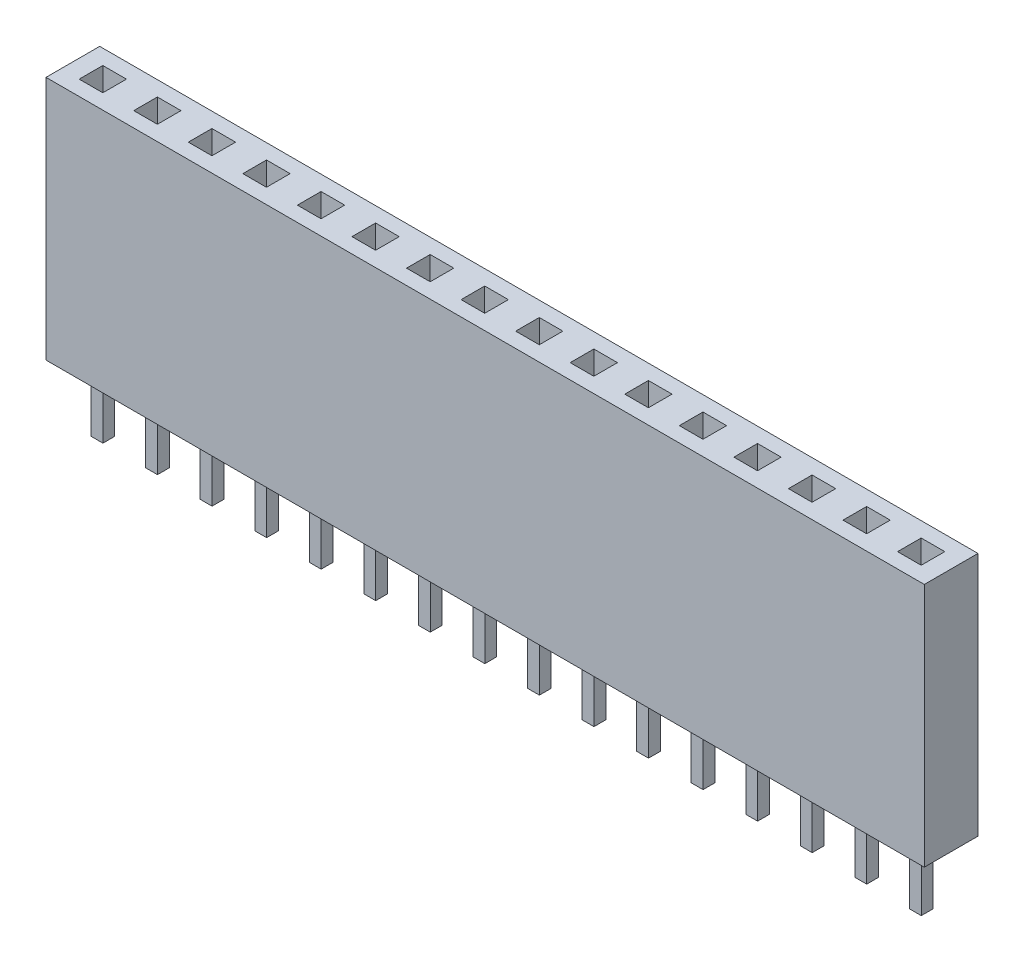
SolidWorks part; units mm, degrees
ref_plane "Front Plane" through (0, 0, 0) normal (0, 0, 1) x (1, 0, 0)
ref_plane "Top Plane" through (0, 0, 0) normal (0, 1, 0) x (1, 0, 0)
ref_plane "Right Plane" through (0, 0, 0) normal (1, 0, 0) x (0, 0, -1)
sketch "Sketch1" plane through (0, 0, 0) normal (0, 0, 1) x (1, 0, 0)
  line L1 (0, 0) -> (40.89, 0)
  line L2 (0, 0) -> (0, 11.4)
  line L3 (0, 11.4) -> (40.89, 11.4)
  line L4 (40.89, 0) -> (40.89, 11.4)
  dimension "D1" = 11.4
  dimension "D2" = 40.89
extrude "Boss-Extrude1" add sketch "Sketch1" along normal mid plane 2.5
sketch "Sketch2" plane through (0, 0, 0) normal (0, -1, 0) x (1, 0, 0)
  line L0 (0, 0) -> (40.89, 0) construction
  line L1 (40.89, 1.25) -> (40.89, -1.25) construction
  line L2 (3.385, -0.55) -> (4.485, -0.55)
  line L3 (0.845, -0.55) -> (1.945, -0.55)
  line L4 (0.845, -0.55) -> (0.845, 0.55)
  line L5 (0.845, 0.55) -> (1.945, 0.55)
  line L6 (1.945, -0.55) -> (1.945, 0.55)
  line L7 (0.845, -0.55) -> (1.945, 0.55) construction
  line L8 (0.845, 0.55) -> (1.945, -0.55) construction
  line L9 (3.385, -0.55) -> (3.385, 0.55)
  line L10 (3.385, 0.55) -> (4.485, 0.55)
  line L11 (4.485, -0.55) -> (4.485, 0.55)
  line L12 (3.385, -0.55) -> (4.485, 0.55) construction
  line L13 (3.385, 0.55) -> (4.485, -0.55) construction
  line L14 (5.925, -0.55) -> (7.025, -0.55)
  line L15 (5.925, -0.55) -> (5.925, 0.55)
  line L16 (5.925, 0.55) -> (7.025, 0.55)
  line L17 (7.025, -0.55) -> (7.025, 0.55)
  line L18 (5.925, -0.55) -> (7.025, 0.55) construction
  line L19 (5.925, 0.55) -> (7.025, -0.55) construction
  line L20 (8.465, -0.55) -> (9.565, -0.55)
  line L21 (8.465, -0.55) -> (8.465, 0.55)
  line L22 (8.465, 0.55) -> (9.565, 0.55)
  line L23 (9.565, -0.55) -> (9.565, 0.55)
  line L24 (8.465, -0.55) -> (9.565, 0.55) construction
  line L25 (8.465, 0.55) -> (9.565, -0.55) construction
  line L26 (11.005, -0.55) -> (12.105, -0.55)
  line L27 (11.005, -0.55) -> (11.005, 0.55)
  line L28 (11.005, 0.55) -> (12.105, 0.55)
  line L29 (12.105, -0.55) -> (12.105, 0.55)
  line L30 (11.005, -0.55) -> (12.105, 0.55) construction
  line L31 (11.005, 0.55) -> (12.105, -0.55) construction
  line L32 (13.545, -0.55) -> (14.645, -0.55)
  line L33 (13.545, -0.55) -> (13.545, 0.55)
  line L34 (13.545, 0.55) -> (14.645, 0.55)
  line L35 (14.645, -0.55) -> (14.645, 0.55)
  line L36 (13.545, -0.55) -> (14.645, 0.55) construction
  line L37 (13.545, 0.55) -> (14.645, -0.55) construction
  line L38 (16.085, -0.55) -> (17.185, -0.55)
  line L39 (16.085, -0.55) -> (16.085, 0.55)
  line L40 (16.085, 0.55) -> (17.185, 0.55)
  line L41 (17.185, -0.55) -> (17.185, 0.55)
  line L42 (16.085, -0.55) -> (17.185, 0.55) construction
  line L43 (16.085, 0.55) -> (17.185, -0.55) construction
  line L44 (18.625, -0.55) -> (19.725, -0.55)
  line L45 (18.625, -0.55) -> (18.625, 0.55)
  line L46 (18.625, 0.55) -> (19.725, 0.55)
  line L47 (19.725, -0.55) -> (19.725, 0.55)
  line L48 (18.625, -0.55) -> (19.725, 0.55) construction
  line L49 (18.625, 0.55) -> (19.725, -0.55) construction
  line L50 (21.165, -0.55) -> (22.265, -0.55)
  line L51 (21.165, -0.55) -> (21.165, 0.55)
  line L52 (21.165, 0.55) -> (22.265, 0.55)
  line L53 (22.265, -0.55) -> (22.265, 0.55)
  line L54 (21.165, -0.55) -> (22.265, 0.55) construction
  line L55 (21.165, 0.55) -> (22.265, -0.55) construction
  line L56 (23.705, -0.55) -> (24.805, -0.55)
  line L57 (23.705, -0.55) -> (23.705, 0.55)
  line L58 (23.705, 0.55) -> (24.805, 0.55)
  line L59 (24.805, -0.55) -> (24.805, 0.55)
  line L60 (23.705, -0.55) -> (24.805, 0.55) construction
  line L61 (23.705, 0.55) -> (24.805, -0.55) construction
  line L62 (26.245, -0.55) -> (27.345, -0.55)
  line L63 (26.245, -0.55) -> (26.245, 0.55)
  line L64 (26.245, 0.55) -> (27.345, 0.55)
  line L65 (27.345, -0.55) -> (27.345, 0.55)
  line L66 (26.245, -0.55) -> (27.345, 0.55) construction
  line L67 (26.245, 0.55) -> (27.345, -0.55) construction
  line L68 (28.785, -0.55) -> (29.885, -0.55)
  line L69 (28.785, -0.55) -> (28.785, 0.55)
  line L70 (28.785, 0.55) -> (29.885, 0.55)
  line L71 (29.885, -0.55) -> (29.885, 0.55)
  line L72 (28.785, -0.55) -> (29.885, 0.55) construction
  line L73 (28.785, 0.55) -> (29.885, -0.55) construction
  line L78 (1.395, 0) -> (3.935, 0) construction
  line L98 (31.325, -0.55) -> (32.425, -0.55)
  line L99 (31.325, -0.55) -> (31.325, 0.55)
  line L100 (31.325, 0.55) -> (32.425, 0.55)
  line L101 (32.425, -0.55) -> (32.425, 0.55)
  line L102 (33.865, -0.55) -> (34.965, -0.55)
  line L103 (33.865, -0.55) -> (33.865, 0.55)
  line L104 (33.865, 0.55) -> (34.965, 0.55)
  line L105 (34.965, -0.55) -> (34.965, 0.55)
  line L106 (36.405, -0.55) -> (37.505, -0.55)
  line L107 (36.405, -0.55) -> (36.405, 0.55)
  line L108 (36.405, 0.55) -> (37.505, 0.55)
  line L109 (37.505, -0.55) -> (37.505, 0.55)
  line L110 (38.945, -0.55) -> (40.045, -0.55)
  line L111 (38.945, -0.55) -> (38.945, 0.55)
  line L112 (38.945, 0.55) -> (40.045, 0.55)
  line L113 (40.045, -0.55) -> (40.045, 0.55)
  line L114 (31.325, -0.55) -> (32.425, 0.55) construction
  line L115 (31.325, 0.55) -> (32.425, -0.55) construction
  line L116 (33.865, -0.55) -> (34.965, 0.55) construction
  line L117 (33.865, 0.55) -> (34.965, -0.55) construction
  line L118 (36.405, -0.55) -> (37.505, 0.55) construction
  line L119 (36.405, 0.55) -> (37.505, -0.55) construction
  line L120 (38.945, -0.55) -> (40.045, 0.55) construction
  line L121 (38.945, 0.55) -> (40.045, -0.55) construction
  point P5 (1.395, 0)
  point P10 (36.955, 0)
  point P11 (34.415, 0)
  point P12 (3.935, 0)
  point P17 (6.475, 0)
  point P22 (9.015, 0)
  point P27 (11.555, 0)
  point P32 (14.095, 0)
  point P37 (16.635, 0)
  point P42 (19.175, 0)
  point P47 (21.715, 0)
  point P52 (24.255, 0)
  point P57 (26.795, 0)
  point P62 (29.335, 0)
  point P67 (39.495, 0)
  point P68 (31.875, 0)
  dimension "D1" = 1.1
  dimension "D3" = 1.395
  dimension "D4" = 2.54
  dimension "D2" = 16
extrude "Cut-Extrude1" cut sketch "Sketch2" against normal through all contours L3 L6 L5 L4 | L2 L11 L10 L9 | L14 L17 L16 L15 | L20 L23 L22 L21 | L26 L29 L28 L27 | L32 L35 L34 L33 | L38 L41 L40 L39 | L110 L113 L112 L111 | L106 L109 L108 L107 | L102 L105 L104 L103 | L98 L101 L100 L99 | L68 L71 L70 L69 | L62 L65 L64 L63 | L56 L59 L58 L57 | L50 L53 L52 L51 | L44 L47 L46 L45 region at (3.935, 0, 0) region at (1.395, 0, 0) region at (6.475, 0, 0) region at (9.015, 0, 0) region at (11.555, 0, 0) region at (14.095, 0, 0) region at (16.635, 0, 0) region at (19.175, 0, 0) region at (21.715, 0, 0) region at (24.255, 0, 0) region at (26.795, 0, 0) region at (29.335, 0, 0) region at (31.875, 0, 0) region at (34.415, 0, 0) region at (36.955, 0, 0) region at (39.495, 0, 0)
sketch "Sketch3" plane through (0, 0, 0) normal (0, -1, 0) x (1, 0, 0)
  line L1 (0, 1.25) -> (40.89, 1.25)
  line L2 (0, 1.25) -> (0, -1.25)
  line L3 (0, -1.25) -> (40.89, -1.25)
  line L4 (40.89, 1.25) -> (40.89, -1.25)
extrude "Boss-Extrude2" add sketch "Sketch3" against normal blind 1
sketch "Sketch4" plane through (0, 0, 0) normal (0, -1, 0) x (1, 0, 0)
  line L0 (1.125, 0) -> (1.675, 0) construction
  line L1 (1.125, 0.275) -> (1.675, 0.275)
  line L2 (1.125, 0.275) -> (1.125, -0.275)
  line L3 (1.125, -0.275) -> (1.675, -0.275)
  line L4 (1.675, 0.275) -> (1.675, -0.275)
  line L5 (0, 0) -> (40.89, 0) construction
  line L6 (40.89, 1.25) -> (40.89, -1.25) construction
  line L7 (0, 1.25) -> (0, -1.25) construction
  line L8 (3.665, 0.275) -> (3.665, -0.275)
  line L9 (3.665, 0.275) -> (4.215, 0.275)
  line L10 (3.665, -0.275) -> (4.215, -0.275)
  line L11 (4.215, 0.275) -> (4.215, -0.275)
  line L12 (6.205, 0.275) -> (6.205, -0.275)
  line L13 (6.205, 0.275) -> (6.755, 0.275)
  line L14 (6.205, -0.275) -> (6.755, -0.275)
  line L15 (6.755, 0.275) -> (6.755, -0.275)
  line L16 (8.745, 0.275) -> (8.745, -0.275)
  line L17 (8.745, 0.275) -> (9.295, 0.275)
  line L18 (8.745, -0.275) -> (9.295, -0.275)
  line L19 (9.295, 0.275) -> (9.295, -0.275)
  line L20 (11.285, 0.275) -> (11.285, -0.275)
  line L21 (11.285, 0.275) -> (11.835, 0.275)
  line L22 (11.285, -0.275) -> (11.835, -0.275)
  line L23 (11.835, 0.275) -> (11.835, -0.275)
  line L24 (13.825, 0.275) -> (13.825, -0.275)
  line L25 (13.825, 0.275) -> (14.375, 0.275)
  line L26 (13.825, -0.275) -> (14.375, -0.275)
  line L27 (14.375, 0.275) -> (14.375, -0.275)
  line L28 (16.365, 0.275) -> (16.365, -0.275)
  line L29 (16.365, 0.275) -> (16.915, 0.275)
  line L30 (16.365, -0.275) -> (16.915, -0.275)
  line L31 (16.915, 0.275) -> (16.915, -0.275)
  line L32 (18.905, 0.275) -> (18.905, -0.275)
  line L33 (18.905, 0.275) -> (19.455, 0.275)
  line L34 (18.905, -0.275) -> (19.455, -0.275)
  line L35 (19.455, 0.275) -> (19.455, -0.275)
  line L36 (21.445, 0.275) -> (21.445, -0.275)
  line L37 (21.445, 0.275) -> (21.995, 0.275)
  line L38 (21.445, -0.275) -> (21.995, -0.275)
  line L39 (21.995, 0.275) -> (21.995, -0.275)
  line L40 (23.985, 0.275) -> (23.985, -0.275)
  line L41 (23.985, 0.275) -> (24.535, 0.275)
  line L42 (23.985, -0.275) -> (24.535, -0.275)
  line L43 (24.535, 0.275) -> (24.535, -0.275)
  line L44 (26.525, 0.275) -> (26.525, -0.275)
  line L45 (26.525, 0.275) -> (27.075, 0.275)
  line L46 (26.525, -0.275) -> (27.075, -0.275)
  line L47 (27.075, 0.275) -> (27.075, -0.275)
  line L48 (29.065, 0.275) -> (29.065, -0.275)
  line L49 (29.065, 0.275) -> (29.615, 0.275)
  line L50 (29.065, -0.275) -> (29.615, -0.275)
  line L51 (29.615, 0.275) -> (29.615, -0.275)
  line L52 (1.125, 0.275) -> (3.665, 0.275) construction
  line L53 (31.605, 0.275) -> (31.605, -0.275)
  line L54 (31.605, 0.275) -> (32.155, 0.275)
  line L55 (31.605, -0.275) -> (32.155, -0.275)
  line L56 (32.155, 0.275) -> (32.155, -0.275)
  line L57 (34.145, 0.275) -> (34.145, -0.275)
  line L58 (34.145, 0.275) -> (34.695, 0.275)
  line L59 (34.145, -0.275) -> (34.695, -0.275)
  line L60 (34.695, 0.275) -> (34.695, -0.275)
  line L61 (36.685, 0.275) -> (36.685, -0.275)
  line L62 (36.685, 0.275) -> (37.235, 0.275)
  line L63 (36.685, -0.275) -> (37.235, -0.275)
  line L64 (37.235, 0.275) -> (37.235, -0.275)
  line L65 (39.225, 0.275) -> (39.225, -0.275)
  line L66 (39.225, 0.275) -> (39.775, 0.275)
  line L67 (39.225, -0.275) -> (39.775, -0.275)
  line L68 (39.775, 0.275) -> (39.775, -0.275)
  point P6 (1.4, 0)
  dimension "D1" = 0.55
  dimension "D2" = 1.4
  dimension "D4" = 2.54
  dimension "D3" = 16
extrude "Boss-Extrude3" add sketch "Sketch4" along normal blind 3 separate body
ref_axis "Axis1" through (1.395, 0, 0) along (0, -1, 0)
ref_axis "Axis2" through (39.495, 0, 0) along (0, -1, 0)
